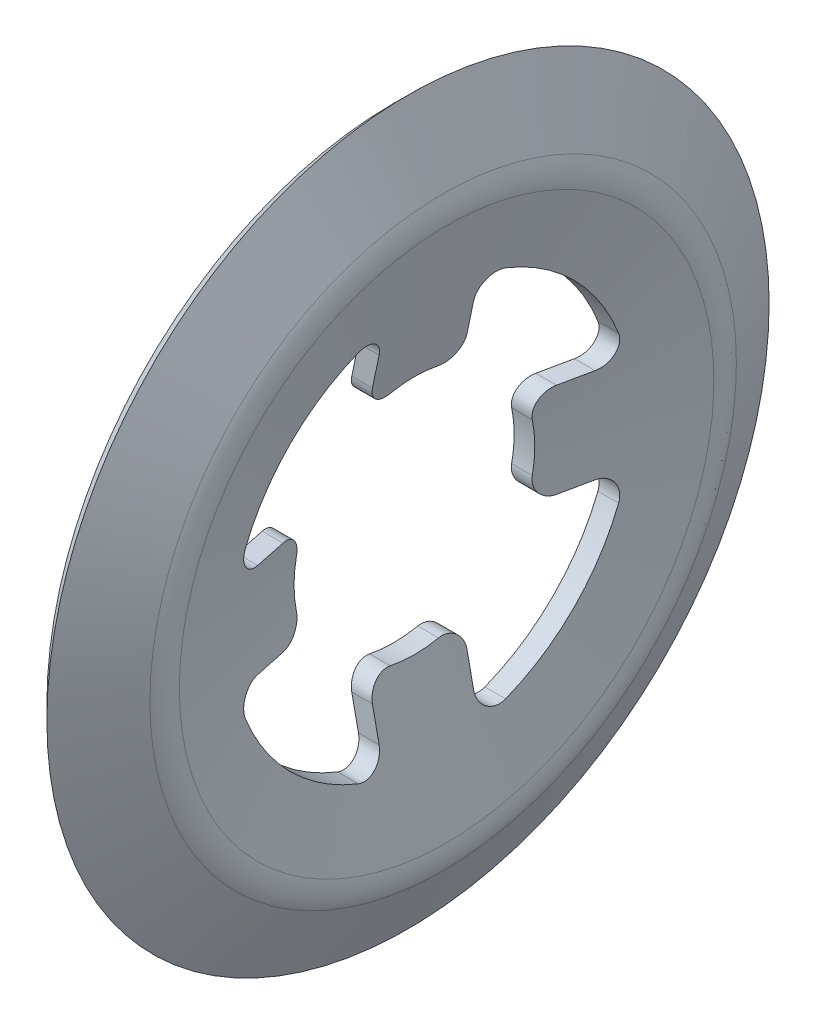
SolidWorks part; units mm, degrees
ref_plane "Front Plane" through (0, 0, 0) normal (0, 0, 1) x (1, 0, 0)
ref_plane "Top Plane" through (0, 0, 0) normal (0, 1, 0) x (1, 0, 0)
ref_plane "Right Plane" through (0, 0, 0) normal (1, 0, 0) x (0, 0, -1)
sketch "Sketch1" plane through (0, 0, 0) normal (1, 0, 0) x (0, 0, -1)
  line L0 (-4.7625, 0) -> (4.7625, 0) construction
  line L1 (-1.5875, 0) -> (1.5875, 0) construction
  line L2 (0, 1.5875) -> (0, 2.6458) construction
  line L3 (0, 2.6458) -> (0, 3.7042) construction
  line L4 (0, 3.7042) -> (0, 4.7625) construction
  circle A0 centre (0, 0) radius 4.7625 construction
  circle A1 centre (0, 0) radius 1.5875 construction
  dimension "Ring OD" = 9.525
  dimension "For OD" = 3.175
sketch "Sketch3" plane through (0, 0, 0) normal (0, 0, 1) x (1, 0, 0)
  line L0 (-0.3683, 0) -> (0.3683, 0) construction
  line L1 (0, -4.7625) -> (0, 4.7625) construction
  line L2 (-0.3683, 4.7625) -> (0.3683, 4.7625) construction
  line L3 (-0.3683, 4.7625) -> (-0.3683, -4.7625) construction
  line L4 (-0.3683, -4.7625) -> (0.3683, -4.7625) construction
  line L5 (0.3683, 4.7625) -> (0.3683, -4.7625) construction
  line L6 (0, 3.7042) -> (0.3683, 3.7042) construction
  line L7 (-0.1799, 4.7625) -> (-0.3683, 4.5741) construction
  line L8 (-0.3683, 4.5741) -> (0.0915, 3.6862) construction
  line L9 (0.0915, 3.6862) -> (-0.3683, 1.5875) construction
  line L10 (-0.3683, 1.5875) -> (-0.3683, 0) construction
  line L11 (-0.3683, 0) -> (1.1049, 0) construction
  line L13 (-0.1799, 4.7625) -> (0.3683, 3.7042) construction
  line L14 (0.3683, 3.7042) -> (-0.1143, 1.5016) construction
  line L15 (-0.1143, 1.5016) -> (-0.1143, 0) construction
  line L17 (0.127, 2.6029) -> (-0.1333, 2.6599) construction
  line L18 (1.1049, 1.5016) -> (-0.3683, 1.5016) construction
  line L19 (1.1049, 1.5016) -> (1.1049, -1.5016) construction
  line L20 (1.1049, -1.5016) -> (-0.3683, -1.5016) construction
  line L21 (-0.3683, 1.5016) -> (-0.3683, -1.5016) construction
  point P9 (0, -4.7625)
  point P12 (-0.1143, 1.5016)
  dimension "Height" = 0.7366
  dimension "D1" = 45
  dimension "D2" = 0.254
  dimension "Ring Thickness" = 0.254
  dimension "Minimum Installation Depth" = 1.4732
sketch "Sketch4" plane through (0, 0, 0) normal (0, 0, 1) x (1, 0, 0)
  line L0 (-0.3683, 4.5741) -> (-0.1799, 4.7625)
  line L1 (-0.1799, 4.7625) -> (0.3683, 3.7042)
  line L2 (0.3683, 3.7042) -> (-0.1143, 1.5016)
  line L3 (-0.1143, 1.5016) -> (-0.1143, 0)
  line L4 (-0.1143, 0) -> (-0.3683, 0)
  line L5 (-0.3683, 0) -> (-0.3683, 1.5875)
  line L6 (-0.3683, 1.5875) -> (0.0915, 3.6862)
  line L7 (0.0915, 3.6862) -> (-0.3683, 4.5741)
  line L8 (-0.3683, 4.5741) -> (0.0915, 3.6862) construction
  line L9 (0.3683, 3.7042) -> (-0.1143, 1.5016) construction
revolve "Revolve1" add sketch "Sketch4" angle 360 about L0
sketch "Sketch7" plane through (0, 0, 0) normal (1, 0, 0) x (0, 0, -1)
  line L0 (0, 4.7625) -> (0, 3.7042) construction
  line L1 (-1.8709, 1.8709) -> (-0.6236, 1.8709) construction
  line L2 (-1.8709, 1.8709) -> (0, 0)
  line L3 (0, 0) -> (1.8709, 1.8709)
  line L4 (-0.6236, 1.8709) -> (0.6236, 1.8709) construction
  line L5 (-0.6236, 2.5713) -> (-0.6236, 1.4599)
  line L6 (-0.6236, 1.4599) -> (0.6236, 1.4599) construction
  line L7 (0.6236, 1.4599) -> (0.6236, 2.5713)
  line L8 (0.6236, 1.8709) -> (1.8709, 1.8709) construction
  arc A0 (1.8709, 1.8709) -> (0.6236, 2.5713) centre (0, 0) ccw
  circle A1 centre (0, 0) radius 3.7042 construction
  arc A2 (-0.6236, 2.5713) -> (-1.8709, 1.8709) centre (0, 0) ccw
  circle A3 centre (0, 0) radius 1.5875 construction
  arc A4 (-0.6236, 1.4599) -> (0.6236, 1.4599) centre (0, 0) cw
  arc A5 (-0.6236, 2.5713) -> (0.6236, 2.5713) centre (0, 0) cw construction
  dimension "Prong Angle" = 90
extrude "Cut-Extrude2" cut sketch "Sketch7" against normal through all both and the other way through all
fillet "Fillet2" radius 0.254 4 edges at (0, 2.5713, 0.6236) (-0.2319, 1.4599, 0.6236) (-0.2319, 1.4599, -0.6236) (0, 2.5713, -0.6236)
pattern_circular "CirPattern3" count 4 over 360 about axis through (-0.3683, 0, 0) along (1, 0, 0) of "Cut-Extrude2", "Fillet2" reverse direction yes
fillet "Fillet3" radius 0.508 2 edges at (0.3683, 0, 3.7042) (0.0915, 0, 3.6862)
equation "\"D2@Sketch3\"=\"Ring Thickness@Sketch3\""
